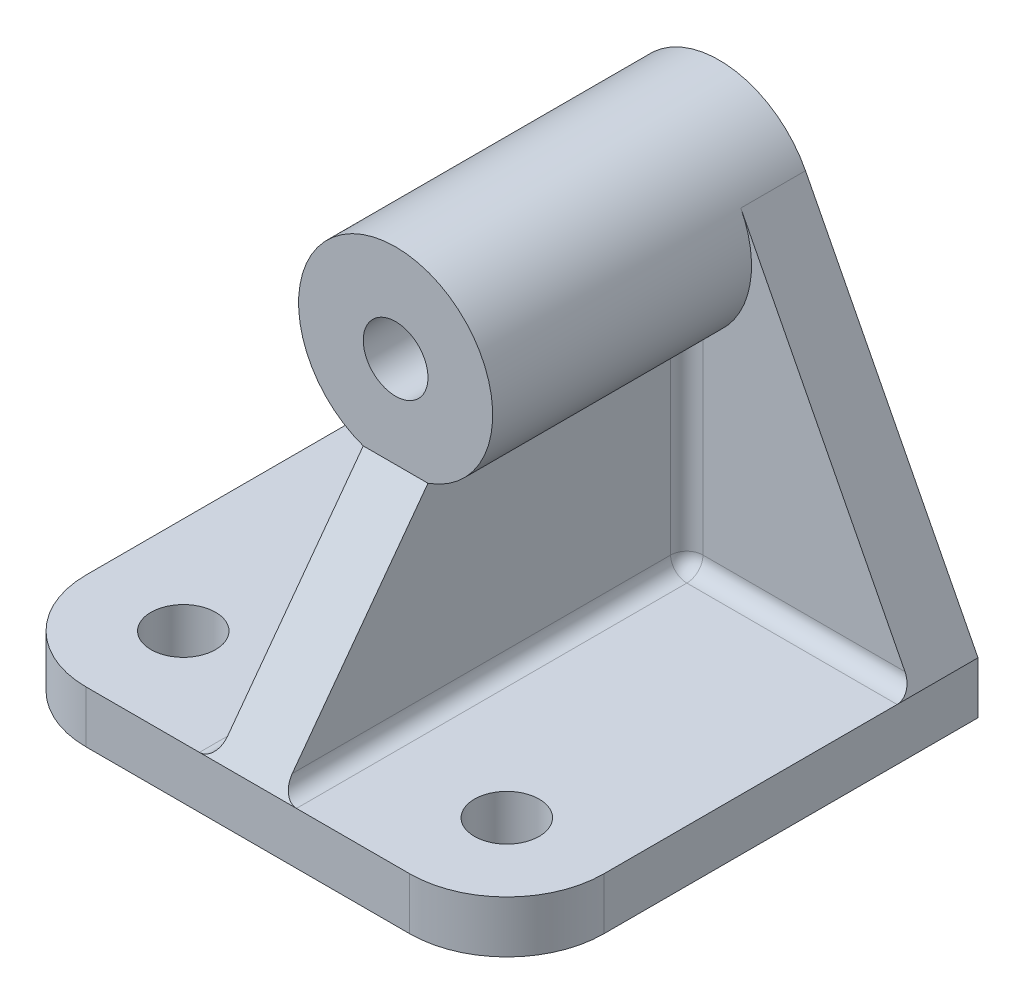
SolidWorks part; units mm, degrees
ref_plane "Front Plane" through (0, 0, 0) normal (0, 0, 1) x (1, 0, 0)
ref_plane "Top Plane" through (0, 0, 0) normal (0, 1, 0) x (1, 0, 0)
ref_plane "Right Plane" through (0, 0, 0) normal (1, 0, 0) x (0, 0, -1)
sketch "Sketch2" plane through (0, 0, 0) normal (1, 0, 0) x (0, 0, -1)
  line L1 (-72.8179, 8.0306) -> (72.8179, 8.0306)
  line L2 (-72.8179, 8.0306) -> (-72.8179, -8.0306)
  line L3 (-72.8179, -8.0306) -> (72.8179, -8.0306)
  line L4 (72.8179, 8.0306) -> (72.8179, -8.0306)
  point P4 (0, -8.0306)
  point P6 (-72.8179, 0)
  dimension "D1" = 145.6358
  dimension "D2" = 16.0611
extrude "Boss-Extrude1" add sketch "Sketch2" along normal mid plane 160
sketch "Sketch3" plane through (0, 8.0306, 0) normal (0, 1, 0) x (1, 0, 0)
  line L0 (80, -72.8179) -> (-80, -72.8179) construction
  line L1 (80, 72.8179) -> (80, -72.8179) construction
  line L2 (-80, 72.8179) -> (-80, -72.8179) construction
  circle A0 centre (50, -42.8179) radius 10
  circle A1 centre (-50, -42.8179) radius 10
  dimension "D1" = 20
  dimension "D3" = 30
  dimension "D4" = 30
  dimension "D5" = 30
  dimension "D2" = 30
extrude "Cut-Extrude1" cut sketch "Sketch3" against normal through all
sketch "Sketch4" plane through (0, 0, -72.8179) normal (0, 0, -1) x (-1, 0, 0)
  line L0 (-80, 8.0306) -> (80, 8.0306) construction
  line L1 (-80, 8.0306) -> (-26.6808, 111.7468)
  line L2 (80, 8.0306) -> (26.6808, 111.7468)
  circle A0 centre (0, 98.0306) radius 30
  circle A1 centre (0, 98.0306) radius 10
  line M3 (80, 8.0306) -> (-80, 8.0306)
  dimension "D1" = 60
  dimension "D2" = 20
  dimension "D3" = 90
extrude "Boss-Extrude2" add sketch "Sketch4" against normal blind 20 contours A0 L1 L2 M3 region at (0, 41.022, -72.8179)
sketch "Sketch5" plane through (0, 0, -72.8179) normal (0, 0, -1) x (-1, 0, 0)
  circle A0 centre (0, 98.0306) radius 30
  circle A1 centre (0, 98.0306) radius 10
  dimension "D1" = 60
  dimension "D2" = 20
extrude "Boss-Extrude3" add sketch "Sketch5" against normal blind 100
fillet "Fillet1" radius 5 1 edges at (0, 8.0306, -52.8179)
sketch "Sketch12" plane through (0, 0, 27.1821) normal (0, 0, 1) x (1, 0, 0)
  line L0 (10, 69.7463) -> (10, 8.0306)
  line L2 (-10, 69.7463) -> (-10, 8.0306)
  line L3 (-10, 8.0306) -> (10, 8.0306)
  line L4 (80, 8.0306) -> (-80, 8.0306) construction
  circle A0 centre (0, 98.0306) radius 30 construction
  arc A1 (-26.6808, 111.7468) -> (26.6808, 111.7468) centre (0, 98.0306) ccw construction
  arc A2 (-10, 69.7463) -> (10, 69.7463) centre (0, 98.0306) ccw
  dimension "D1" = 20
  dimension "D2" = 10
extrude "Boss-Extrude9" add sketch "Sketch12" against normal up to surface (80 mm away) up to face at (0, 51.4596, -52.8179)
sketch "Sketch14" plane through (0, 0, 0) normal (1, 0, 0) x (0, 0, -1)
  line L0 (-27.1821, 69.7463) -> (-72.8179, 8.0306)
  line L1 (-72.8179, 8.0306) -> (-27.1821, 8.0306)
  line L2 (-27.1821, 8.0306) -> (-27.1821, 69.7463)
extrude "Boss-Extrude10" add sketch "Sketch14" along normal mid plane 20
fillet "Fillet2" radius 5 6 edges at (-10, 41.3884, -52.8179) (-10, 9.495, -51.3534) (10, 41.3884, -52.8179) (10, 9.495, -51.3534) (-10, 8.0306, 12.5) (10, 8.0306, 12.5)
fillet "Fillet3" radius 30 2 edges at (80, 0, 72.8179) (-80, 0, 72.8179)
